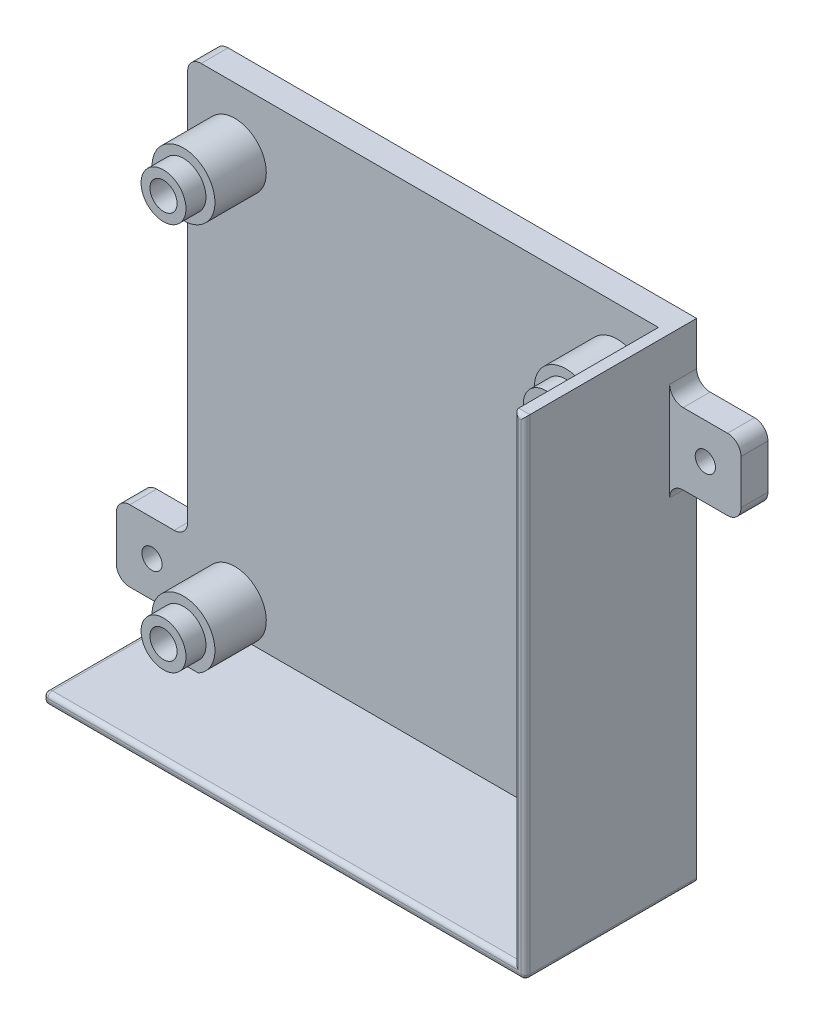
SolidWorks part; units mm, degrees
material "Custom Plastic"
ref_plane "X-Y Datum" through (0, 0, 0) normal (0, 0, 1) x (1, 0, 0)
ref_plane "X-Z Datum" through (0, 0, 0) normal (0, 1, 0) x (1, 0, 0)
ref_plane "Y-Z Datum" through (0, 0, 0) normal (1, 0, 0) x (0, 0, -1)
sketch "Sketch1" plane through (0, 0, 0) normal (0, 0, 1) x (1, 0, 0)
  line L1 (-52.3875, 53.1812) -> (52.3875, 53.1812)
  line L2 (-52.3875, 53.1812) -> (-52.3875, -53.1812)
  line L3 (-52.3875, -53.1812) -> (52.3875, -53.1812)
  line L4 (52.3875, 53.1812) -> (52.3875, -53.1812)
  line L5 (-52.3875, 53.1812) -> (52.3875, -53.1812) construction
  line L6 (-52.3875, -53.1812) -> (52.3875, 53.1812) construction
  point P0 (0, 0)
  dimension "D1" = 104.775
  dimension "D2" = 106.3625
extrude "Boss-Extrude1" add sketch "Sketch1" along normal blind 6
sketch "Sketch2" plane through (0, 0, 0) normal (0, 0, 1) x (1, 0, 0)
  line L3 (-52.3875, -53.1812) -> (-52.3875, -55.6812)
  line L4 (54.8875, 53.1812) -> (52.3875, 53.1812)
  line L5 (54.8875, -55.6812) -> (54.8875, 53.1812)
  line L6 (-52.3875, -55.6812) -> (54.8875, -55.6812)
  line L7 (54.8875, -55.6812) -> (54.8875, 53.1812)
  line L8 (-52.3875, -55.6812) -> (54.8875, -55.6812)
  line L9 (52.3875, -53.1812) -> (52.3875, 53.1812) construction
  line L10 (-52.3875, -53.1812) -> (52.3875, -53.1812) construction
  line L11 (52.3875, -53.1812) -> (52.3875, 53.1812)
  line L12 (-52.3875, -53.1812) -> (52.3875, -53.1812)
  dimension "D1" = 2.5
extrude "Boss-Extrude2" add sketch "Sketch2" along normal blind 38.1
sketch "Sketch3" plane through (0, 0, 6) normal (0, 0, 1) x (1, 0, 0)
  circle A0 centre (-41.882, 39.351) radius 3.025
  circle A1 centre (43.208, 39.351) radius 3.025
  circle A2 centre (43.208, -47.009) radius 3.025
  circle A3 centre (-41.882, -47.009) radius 3.025
  circle A4 centre (43.208, 39.351) radius 5
  circle A5 centre (-41.882, 39.351) radius 5
  circle A6 centre (-41.882, -47.009) radius 5
  circle A7 centre (43.208, -47.009) radius 5
  point P0 (-41.882, 39.351)
  point P1 (-41.882, -47.009)
  point P3 (43.208, -47.009)
  point P5 (43.208, 39.351)
  dimension "D1" = 6.05
  dimension "D2" = 10
extrude "Boss-Extrude3" add sketch "Sketch3" along normal blind 15.875
sketch "Sketch4" plane through (0, 0, 6) normal (0, 0, 1) x (1, 0, 0)
  circle A0 centre (43.208, 39.351) radius 7
  circle A1 centre (-41.882, 39.351) radius 7
  circle A2 centre (-41.882, -47.009) radius 7
  circle A3 centre (43.208, -47.009) radius 7
  circle A5 centre (-41.882, -47.009) radius 3.025
  circle A6 centre (-41.882, -47.009) radius 3.025
  circle A7 centre (43.208, -47.009) radius 3.025
  circle A8 centre (43.208, -47.009) radius 3.025
  circle A9 centre (43.208, 39.351) radius 3.025
  circle A10 centre (43.208, 39.351) radius 3.025
  circle A11 centre (-41.882, 39.351) radius 3.025
  circle A12 centre (-41.882, 39.351) radius 3.025
  dimension "D1" = 14
  dimension "D2" = 0
  dimension "D3" = 0
  dimension "D4" = 0
  dimension "D5" = 0
extrude "Boss-Extrude4" add sketch "Sketch4" along normal blind 11.43
sketch "Sketch6" plane through (0, 0, 0) normal (0, 0, 1) x (1, 0, 0)
  line L0 (-68.2625, -39.8062) -> (-52.3875, -55.6812)
  line L1 (-52.3875, -55.6812) -> (-68.2625, -55.6812)
  line L2 (-52.3875, -55.6812) -> (-52.3875, -39.8062)
  line L3 (-52.3875, -39.8062) -> (-68.2625, -39.8062)
  line L4 (-68.2625, -55.6812) -> (-68.2625, -39.8062)
  line L5 (54.8875, -55.6812) -> (54.8875, 53.1812) construction
  line L6 (54.8875, 40.4812) -> (70.7625, 40.4812)
  line L7 (54.8875, 40.4812) -> (54.8875, 24.6062)
  line L8 (54.8875, 24.6062) -> (70.7625, 24.6062)
  line L9 (70.7625, 40.4812) -> (70.7625, 24.6062)
  line L10 (54.8875, 24.6062) -> (70.7625, 40.4812)
  line L11 (54.8875, 53.1812) -> (52.3875, 53.1812) construction
  circle A0 centre (-60.325, -47.7437) radius 2 construction
  circle A1 centre (62.825, 32.5437) radius 2 construction
  dimension "D1" = 4
  dimension "D6" = 4
  dimension "D2" = 15.875
  dimension "D3" = 15.875
  dimension "D4" = 15.875
  dimension "D5" = 15.875
  dimension "D7" = 12.7
extrude "Boss-Extrude5" add sketch "Sketch6" along normal blind 6 contours L2 L3 L0 | L4 L1 L0 | L10 L8 L9 | L7 L10 L6 region at (-57.6792, -45.0979, 0) region at (-62.9708, -50.3896, 0) region at (60.1792, 35.1896, 0) region at (65.4708, 29.8979, 0)
hole_wizard "M4 Clearance Hole1" positions "Sketch7" profile "Sketch8" hole size "M4" standard "ANSI Metric" end condition through all
sketch "Sketch7" plane through (0, 0, 6) normal (0, 0, 1) x (1, 0, 0)
  point P0 (62.825, 32.5437)
  point P3 (-60.325, -47.7437)
sketch "Sketch8" plane through (62.825, 32.5437, 6) normal (1, 0, 0) x (0, -1, 0)
  line L0 (0, 0) -> (0, 6)
  line L1 (0, 6) -> (2.25, 6)
  line L2 (2.25, 6) -> (2.25, 0)
  line L5 (2.25, 0) -> (0, 0)
  line L11 (0, -6.35) -> (0, 107.95) construction
  dimension "Thru Hole Dia." = 4.5
  dimension "Thru Hole Depth" = 6
fillet "Fillet2" radius 3 8 edges at (70.7625, 24.6062, 3) (70.7625, 40.4812, 3) (54.8875, 40.4812, 3) (54.8875, 24.6062, 3) (-68.2625, -55.6812, 3) (-68.2625, -39.8062, 3) (-52.3875, -39.8062, 3) (-52.3875, 53.1812, 3)
fillet "Fillet3" radius 1 9 edges at (52.3875, 0, 38.1) (53.6375, 53.1812, 38.1) (54.8875, -1.25, 38.1) (-52.3875, -54.4312, 38.1) (0, -53.1812, 38.1) (54.8875, -55.6812, 19.05) (1.25, -55.6812, 38.1) (-52.3875, -53.1812, 22.05) (-52.3875, -55.6812, 22.05)
